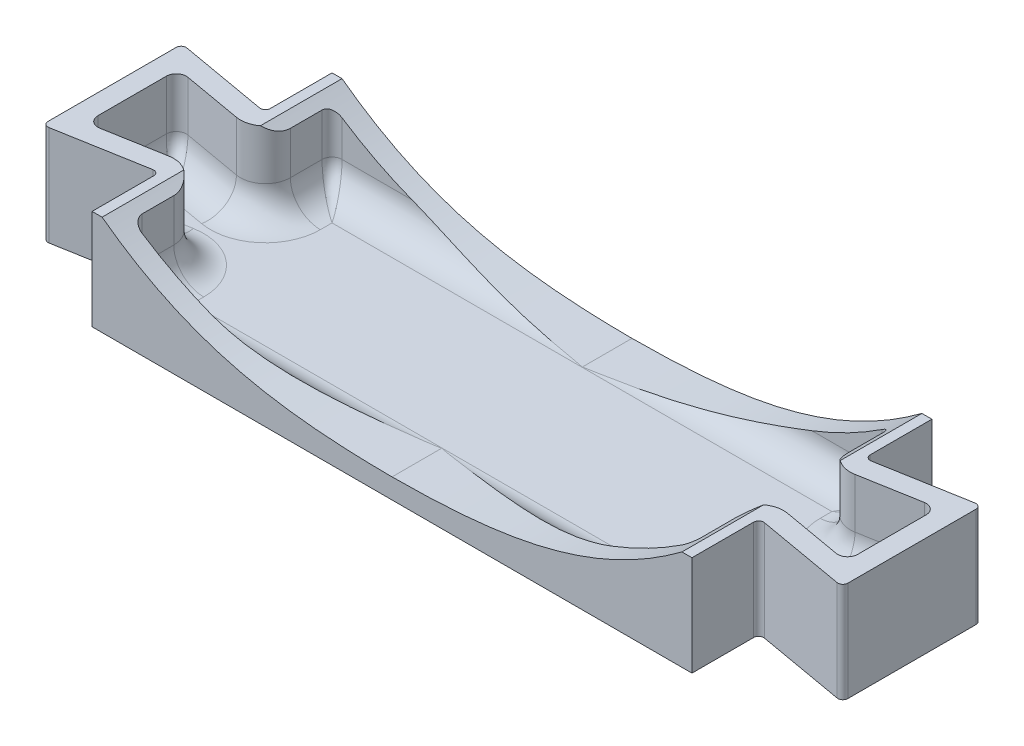
SolidWorks part; units mm, degrees
ref_plane "Front Plane" through (0, 0, 0) normal (0, 0, 1) x (1, 0, 0)
ref_plane "Top Plane" through (0, 0, 0) normal (0, 1, 0) x (1, 0, 0)
ref_plane "Right Plane" through (0, 0, 0) normal (1, 0, 0) x (0, 0, -1)
sketch "Sketch1" plane through (0, 0, 0) normal (0, 1, 0) x (1, 0, 0)
  line L0 (-15, 2.6184) -> (-20, 3.5)
  line L1 (-15, -6) -> (15, -6)
  line L2 (-15, -6) -> (-15, -2.6184)
  line L3 (-15, 6) -> (15, 6)
  line L4 (15, -6) -> (15, -2.6184)
  line L5 (-15, -6) -> (15, 6) construction
  line L6 (-15, 6) -> (15, -6) construction
  line L7 (-20, 3.5) -> (-20, -3.5)
  line L8 (-10, 0) -> (-18.3718, 0) construction
  line L9 (-15, -2.6184) -> (-20, -3.5)
  line L10 (-15, 2.6184) -> (-15, 6)
  line L11 (0, 0) -> (0, 6) construction
  line L12 (15, -2.6184) -> (20, -3.5)
  line L13 (20, 3.5) -> (20, -3.5)
  line L14 (15, 2.6184) -> (20, 3.5)
  line L15 (15, 2.6184) -> (15, 6)
  line L16 (-15, 6) -> (-25.4194, 6) construction
  point P0 (0, 0)
  point P13 (-20, 0)
  dimension "D1" = 12
  dimension "D2" = 30
  dimension "D3" = 3.5
  dimension "D4" = 80
  dimension "D5" = 5
extrude "Boss-Extrude1" add sketch "Sketch1" along normal blind 5
fillet "Fillet1" radius 0.25 8 edges at (-15, 2.5, 2.6184) (-20, 2.5, 3.5) (-20, 2.5, -3.5) (-15, 2.5, -2.6184) (15, 2.5, -2.6184) (20, 2.5, -3.5) (20, 2.5, 3.5) (15, 2.5, 2.6184)
shell "Shell1" thickness 1 removed face at (0, 5, 0)
fillet "Fillet2" radius 0.5 8 edges at (19, 3, 2.3082) (19, 3, -2.3082) (-19, 3, 2.3082) (-19, 3, -2.3082) (-14, 3, 5) (14, 3, 5) (14, 3, -5) (-14, 3, -5)
fillet "Fillet5" radius 1.5 24 edges at (13.8536, 1, -4.8536) (14, 1, -3.7082) (14.4465, 1, -1.9587) (16.9401, 1, -1.945) (18.8214, 1, -2.0954) (19, 1, 0) (18.8214, 1, 2.0954) (16.9401, 1, 1.945) (14.4465, 1, 1.9587) (14, 1, 3.7082) (13.8536, 1, 4.8536) (0, 1, 5) (-13.8536, 1, 4.8536) (-14, 1, 3.7082) (-14.4465, 1, 1.9587) (-16.9401, 1, 1.945) (-18.8214, 1, 2.0954) (-19, 1, 0) (-18.8214, 1, -2.0954) (-16.9401, 1, -1.945) (-14.4465, 1, -1.9587) (-14, 1, -3.7082) (-13.8536, 1, -4.8536) (0, 1, -5)
sketch "Sketch2" plane through (0, 0, 0) normal (0, 0, 1) x (1, 0, 0)
  line L0 (-15, 5) -> (15, 5) construction
  line L1 (0, 0) -> (0, 5) construction
  line L2 (-14.5, 5) -> (-14.5, 5.1779)
  line L3 (-15, 0) -> (15, 0) construction
  line L4 (-14.5, 5.1779) -> (14.5, 5.1779)
  line L5 (14.5, 5) -> (14.5, 5.1779)
  spline S0 degree 3 poles (-14.5, 5) (-10.1117, 1.7437) (-5.6899, 1.0248) (0, 1) knots 0 0 0 0 1 1 1 1
  spline S1 degree 3 poles (14.5, 5) (10.1117, 1.7437) (5.6899, 1.0248) (0, 1) knots 0 0 0 0 1 1 1 1
  point P15 (0, 5.1779)
  dimension "D1" = 14.5
  dimension "D2" = 10
  dimension "D3" = 1
extrude "Cut-Extrude1" cut sketch "Sketch2" against normal mid plane 12
